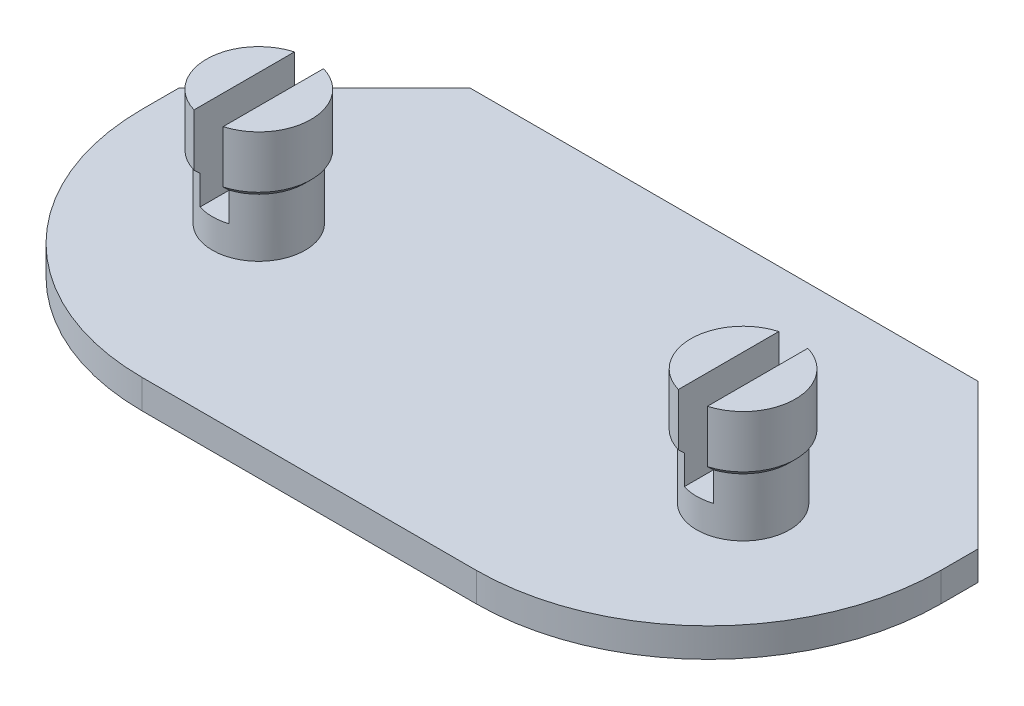
SolidWorks part; units mm, degrees
ref_plane "Front Plane" through (0, 0, 0) normal (0, 0, 1) x (1, 0, 0)
ref_plane "Top Plane" through (0, 0, 0) normal (0, 1, 0) x (1, 0, 0)
ref_plane "Right Plane" through (0, 0, 0) normal (1, 0, 0) x (0, 0, -1)
sketch "Sketch1" plane through (0, 0, 0) normal (0, 1, 0) x (1, 0, 0)
  line L0 (0, 0) -> (0, 11.8039) construction
  line L1 (27.5, -19) -> (-27.5, -19)
  line L2 (27.5, -19) -> (27.5, 19)
  line L3 (27.5, 19) -> (-27.5, 19)
  line L4 (-27.5, -19) -> (-27.5, 19)
  line L5 (27.5, -19) -> (-27.5, 19) construction
  line L6 (27.5, 19) -> (-27.5, -19) construction
  circle A0 centre (-16.675, 3.65) radius 3.4
  circle A1 centre (16.675, 3.65) radius 3.4
  point P0 (0, 0)
  dimension "D3" = 6.8
  dimension "D1" = 55
  dimension "D2" = 38
  dimension "D4" = 15.35
  dimension "D5" = 16.675
sketch "Sketch2" plane through (0, 0, 0) normal (0, 1, 0) x (1, 0, 0)
  line L1 (27.5, -19) -> (-27.5, -19)
  line L2 (27.5, -19) -> (27.5, 19)
  line L3 (27.5, 19) -> (-27.5, 19)
  line L4 (-27.5, -19) -> (-27.5, 19)
  line L5 (27.5, -19) -> (-27.5, 19) construction
  line L6 (27.5, 19) -> (-27.5, -19) construction
  point P0 (0, 0)
  dimension "D1" = 38
extrude "Boss-Extrude1" add sketch "Sketch2" along normal blind 2
sketch "Sketch3" plane through (0, 0, 0) normal (0, 1, 0) x (1, 0, 0)
  line L0 (0, 0) -> (0, 14.4604) construction
  circle A0 centre (-16.675, 3.65) radius 3.2
  circle A2 centre (16.675, 3.65) radius 3.2
extrude "Boss-Extrude2" add sketch "Sketch3" along normal blind 10
sketch "Sketch4" plane through (0, 10, 0) normal (0, 1, 0) x (1, 0, 0)
  line L0 (-16.675, 6.85) -> (-16.675, 0.45) construction
  line L1 (0, -1.1) -> (0, 1.1) construction
  circle A0 centre (-16.675, 3.65) radius 3.2 construction
  circle A1 centre (-16.675, 3.65) radius 3.2 construction
  circle A2 centre (-16.675, 3.65) radius 3.6
  circle A3 centre (16.675, 3.65) radius 3.6
extrude "Boss-Extrude3" add sketch "Sketch4" against normal blind 1
chamfer "Chamfer1" distance 3 angle 45 2 edges at (16.675, 9, -6.85) (-16.675, 9, -0.45)
sketch "Sketch5" plane through (0, 10, 0) normal (0, 1, 0) x (1, 0, 0)
  line L0 (16.675, 7.25) -> (16.675, 0.05) construction
  line L1 (0, -1.1) -> (0, 1.1) construction
  line L2 (17.675, -1.6922) -> (15.675, -1.6922)
  line L3 (17.675, -1.6922) -> (17.675, 8.9922)
  line L4 (17.675, 8.9922) -> (15.675, 8.9922)
  line L5 (15.675, -1.6922) -> (15.675, 8.9922)
  line L6 (17.675, -1.6922) -> (15.675, 8.9922) construction
  line L7 (17.675, 8.9922) -> (15.675, -1.6922) construction
  line L8 (-17.675, 8.9922) -> (-15.675, 8.9922)
  line L9 (-15.675, -1.6922) -> (-15.675, 8.9922)
  line L10 (-17.675, -1.6922) -> (-15.675, -1.6922)
  line L11 (-17.675, -1.6922) -> (-17.675, 8.9922)
  circle A0 centre (16.675, 3.65) radius 3.6 construction
  point P4 (16.675, 3.65)
extrude "Cut-Extrude1" cut sketch "Sketch5" against normal blind 6
chamfer "Chamfer2" distance 10 angle 45 2 edges at (27.5, 1, -19) (-27.5, 1, -19)
ref_plane "Plane3" through (0, 0, 0) normal (-1, 0, 0) x (0, 0, 1)
sketch "Sketch6" plane through (0, 0, 0) normal (-1, 0, 0) x (0, 0, 1)
  line L0 (19, 2) -> (15.55, 4.8284) construction
  line L1 (11.05, 4.8284) -> (9.55, 2)
  line L2 (-9, 2) -> (19, 2) construction
  line L3 (9.55, 2) -> (12.05, 2)
  line L4 (-0.45, 2) -> (-0.45, 4) construction
  circle A0 centre (15.55, 4.8284) radius 3
  arc A1 (12.05, 2) -> (11.05, 4.8284) centre (15.55, 4.8284) ccw
  circle A2 centre (15.55, 4.8284) radius 4.5 construction
  dimension "D1" = 1.5
  dimension "D2" = 6
  dimension "D3" = 9
  dimension "D4" = 6
  dimension "D5" = 16
sketch "Sketch8" plane through (0, 0, 0) normal (-1, 0, 0) x (0, 0, 1)
  line L1 (9.55, 2) -> (19, 2)
  line L2 (9.55, 2) -> (9.55, 0)
  line L3 (9.55, 0) -> (19, 0)
  line L4 (19, 2) -> (19, 0)
extrude "Cut-Extrude2" cut sketch "Sketch8" against normal through all and the other way through all
sketch "Sketch9" plane through (0, 0, 0) normal (-1, 0, 0) x (0, 0, 1)
  line L0 (9.55, 2) -> (11.05, 4.8284)
  line L1 (9.55, 0) -> (12.05, 2)
  line L2 (9.55, 2) -> (9.55, 0)
  circle A0 centre (15.55, 4.8284) radius 3
  arc A1 (12.05, 2) -> (11.05, 4.8284) centre (15.55, 4.8284) ccw
fillet "Fillet2" radius 16 2 edges at (-27.5, 1, 9.55) (27.5, 1, 9.55)
